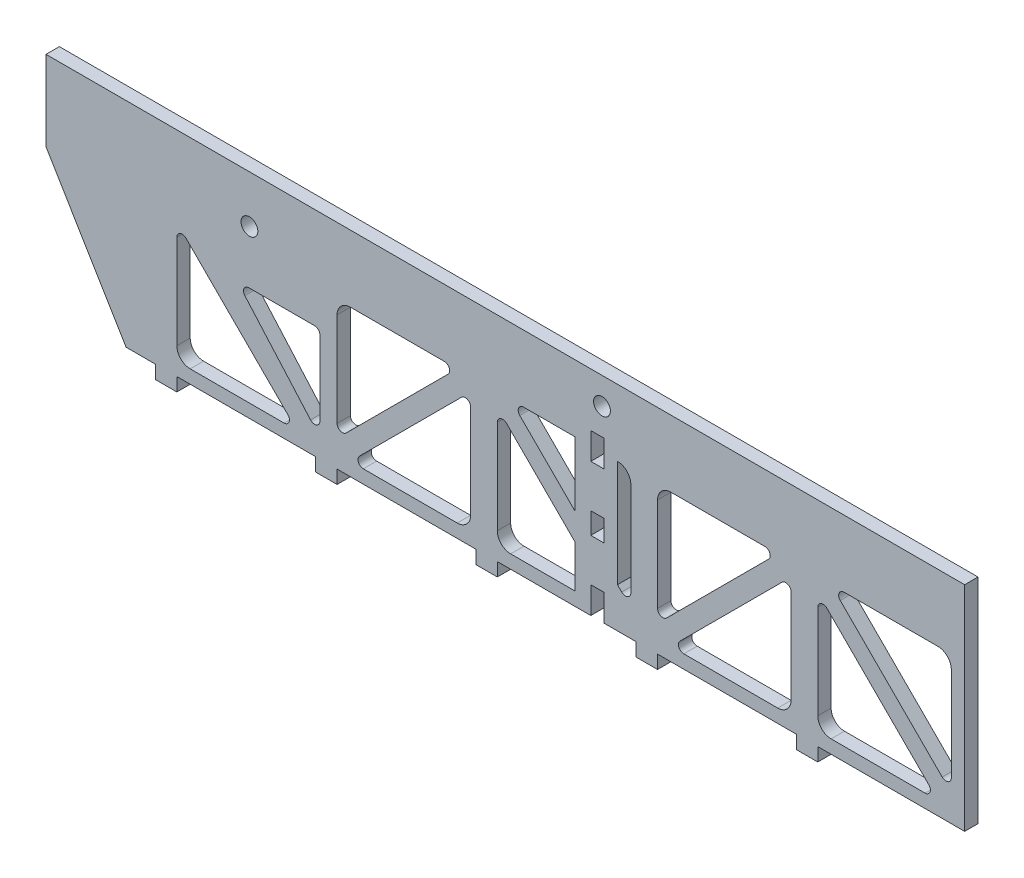
SolidWorks part; units mm, degrees
material "Pine"
ref_plane "Front Plane" through (0, 0, 0) normal (0, 0, 1) x (1, 0, 0)
ref_plane "Top Plane" through (0, 0, 0) normal (0, 1, 0) x (1, 0, 0)
ref_plane "Right Plane" through (0, 0, 0) normal (1, 0, 0) x (0, 0, -1)
sketch "Model" plane through (0, 0, 0) normal (0, 0, 1) x (1, 0, 0)
  line L0 (-306.6281, 15.625) -> (-306.6281, 51.1493)
  line L1 (-309.1681, 53.6893) -> (-340.406, 53.6893)
  line L2 (-342.3135, 49.472) -> (-311.0755, 13.9477)
  line L8 (-171.2321, 6.35) -> (-215.9, 6.35)
  line L9 (-222.25, 57.3679) -> (-222.25, 12.7)
  line L10 (-217.9139, 59.1639) -> (-169.4361, 10.6861)
  line L11 (-234.95, 57.3679) -> (-234.95, 12.7)
  line L12 (-241.3, 6.35) -> (-285.9679, 6.35)
  line L13 (-239.2861, 59.1639) -> (-287.7639, 10.6861)
  line L14 (-294.1139, 17.0361) -> (-245.6361, 65.5139)
  line L15 (-298.45, 63.5) -> (-298.45, 18.8321)
  line L16 (-247.4321, 69.85) -> (-292.1, 69.85)
  line L17 (-323.6321, 6.35) -> (-368.3, 6.35)
  line L18 (-374.65, 57.3679) -> (-374.65, 12.7)
  line L19 (-370.3139, 59.1639) -> (-321.8361, 10.6861)
  line L20 (-18.8321, 6.35) -> (-63.5, 6.35)
  line L21 (-69.85, 57.3679) -> (-69.85, 12.7)
  line L22 (-17.0361, 10.6861) -> (-65.5139, 59.1639)
  line L23 (-82.55, 57.3679) -> (-82.55, 12.7)
  line L24 (-88.9, 6.35) -> (-133.5679, 6.35)
  line L25 (-86.8861, 59.1639) -> (-135.3639, 10.6861)
  line L26 (-93.2361, 65.5139) -> (-141.7139, 17.0361)
  line L27 (-146.05, 63.5) -> (-146.05, 18.8321)
  line L28 (-95.0321, 69.85) -> (-139.7, 69.85)
  line L29 (-163.0861, 17.0361) -> (-211.5639, 65.5139)
  line L30 (-165.1, 69.85) -> (-209.7679, 69.85)
  line L31 (-158.75, 63.5) -> (-158.75, 18.8321)
  line L35 (-398.78, 0) -> (-436.88, 63.5)
  line L36 (0, 0) -> (-398.78, 0)
  line L37 (0, 0) -> (0, 95.25)
  line L38 (0, 95.25) -> (-436.88, 95.25)
  line L39 (-436.88, 63.5) -> (-436.88, 95.25)
  line L40 (-6.35, 63.5) -> (-6.35, 18.8321)
  line L41 (-59.1639, 65.5139) -> (-10.6861, 17.0361)
  line L42 (-12.7, 69.85) -> (-57.3679, 69.85)
  arc A0 (-222.25, 12.7) -> (-215.9, 6.35) centre (-215.9, 12.7) ccw
  arc A1 (-217.9139, 59.1639) -> (-222.25, 57.3679) centre (-219.71, 57.3679) ccw
  arc A2 (-171.2321, 6.35) -> (-169.4361, 10.6861) centre (-171.2321, 8.89) ccw
  arc A3 (-234.95, 57.3679) -> (-239.2861, 59.1639) centre (-237.49, 57.3679) ccw
  arc A4 (-241.3, 6.35) -> (-234.95, 12.7) centre (-241.3, 12.7) ccw
  arc A5 (-287.7639, 10.6861) -> (-285.9679, 6.35) centre (-285.9679, 8.89) ccw
  arc A6 (-245.6361, 65.5139) -> (-247.4321, 69.85) centre (-247.4321, 67.31) ccw
  arc A7 (-298.45, 18.8321) -> (-294.1139, 17.0361) centre (-295.91, 18.8321) ccw
  arc A8 (-292.1, 69.85) -> (-298.45, 63.5) centre (-292.1, 63.5) ccw
  arc A9 (-323.6321, 6.35) -> (-321.8361, 10.6861) centre (-323.6321, 8.89) ccw
  arc A10 (-374.65, 12.7) -> (-368.3, 6.35) centre (-368.3, 12.7) ccw
  arc A11 (-370.3139, 59.1639) -> (-374.65, 57.3679) centre (-372.11, 57.3679) ccw
  arc A12 (-69.85, 12.7) -> (-63.5, 6.35) centre (-63.5, 12.7) ccw
  arc A13 (-65.5139, 59.1639) -> (-69.85, 57.3679) centre (-67.31, 57.3679) ccw
  arc A14 (-18.8321, 6.35) -> (-17.0361, 10.6861) centre (-18.8321, 8.89) ccw
  arc A15 (-82.55, 57.3679) -> (-86.8861, 59.1639) centre (-85.09, 57.3679) ccw
  arc A16 (-88.9, 6.35) -> (-82.55, 12.7) centre (-88.9, 12.7) ccw
  arc A17 (-135.3639, 10.6861) -> (-133.5679, 6.35) centre (-133.5679, 8.89) ccw
  arc A18 (-93.2361, 65.5139) -> (-95.0321, 69.85) centre (-95.0321, 67.31) ccw
  arc A19 (-146.05, 18.8321) -> (-141.7139, 17.0361) centre (-143.51, 18.8321) ccw
  arc A20 (-139.7, 69.85) -> (-146.05, 63.5) centre (-139.7, 63.5) ccw
  arc A21 (-163.0861, 17.0361) -> (-158.75, 18.8321) centre (-161.29, 18.8321) ccw
  arc A22 (-209.7679, 69.85) -> (-211.5639, 65.5139) centre (-209.7679, 67.31) ccw
  arc A23 (-158.75, 63.5) -> (-165.1, 69.85) centre (-165.1, 63.5) ccw
  arc A24 (-306.6281, 15.625) -> (-311.0755, 13.9477) centre (-309.1681, 15.625) cw
  arc A25 (-340.406, 53.6893) -> (-342.3135, 49.472) centre (-340.406, 51.1493) ccw
  arc A26 (-306.6281, 51.1493) -> (-309.1681, 53.6893) centre (-309.1681, 51.1493) ccw
  arc A27 (-10.6861, 17.0361) -> (-6.35, 18.8321) centre (-8.89, 18.8321) ccw
  arc A28 (-57.3679, 69.85) -> (-59.1639, 65.5139) centre (-57.3679, 67.31) ccw
  arc A29 (-6.35, 63.5) -> (-12.7, 69.85) centre (-12.7, 63.5) ccw
  circle A30 centre (-172.466, 88.9) radius 4
  circle A31 centre (-340.148, 79.054) radius 4
  dimension "D2" = 172.466
  dimension "D4" = 8
  dimension "D5" = 167.682
  dimension "D7" = 8
  dimension "D6" = 9.846
  dimension "D8" = 2.54
  dimension "D1" = 95.25
  dimension "D3" = 6.35
extrude "Boss-Extrude1" add sketch "Model" along normal blind 6.35
sketch "Sketch1" plane through (0, 0, 6.35) normal (0, 0, 1) x (1, 0, 0)
  line L0 (-69.85, 95.25) -> (-69.85, 0) construction
  line L1 (-69.85, 57.3679) -> (-69.85, 12.7) construction
  line L2 (-398.78, 0) -> (0, 0) construction
  line L3 (-146.05, 95.25) -> (-146.05, 0) construction
  line L4 (-146.05, 63.5) -> (-146.05, 18.8321) construction
  line L5 (-222.25, 95.25) -> (-222.25, 0) construction
  line L6 (-222.25, 57.3679) -> (-222.25, 12.7) construction
  line L7 (-298.45, 95.25) -> (-298.45, 0) construction
  line L8 (-298.45, 63.5) -> (-298.45, 18.8321) construction
  line L9 (-374.65, 95.25) -> (-374.65, 0) construction
  line L10 (-374.65, 57.3679) -> (-374.65, 12.7) construction
  line L11 (0, 95.25) -> (-436.88, 95.25) construction
  line L12 (-69.85, 0) -> (-80.01, 0)
  line L13 (-69.85, 0) -> (-69.85, -6.35)
  line L14 (-69.85, -6.35) -> (-80.01, -6.35)
  line L15 (-80.01, 0) -> (-80.01, -6.35)
  line L16 (-146.05, 0) -> (-156.21, 0)
  line L17 (-146.05, 0) -> (-146.05, -6.35)
  line L18 (-146.05, -6.35) -> (-156.21, -6.35)
  line L19 (-156.21, 0) -> (-156.21, -6.35)
  line L20 (-222.25, 0) -> (-232.41, 0)
  line L21 (-222.25, 0) -> (-222.25, -6.35)
  line L22 (-222.25, -6.35) -> (-232.41, -6.35)
  line L23 (-232.41, 0) -> (-232.41, -6.35)
  line L24 (-298.45, 0) -> (-308.61, 0)
  line L25 (-298.45, 0) -> (-298.45, -6.35)
  line L26 (-298.45, -6.35) -> (-308.61, -6.35)
  line L27 (-308.61, 0) -> (-308.61, -6.35)
  line L28 (-374.65, 0) -> (-384.81, 0)
  line L29 (-374.65, 0) -> (-374.65, -6.35)
  line L30 (-374.65, -6.35) -> (-384.81, -6.35)
  line L31 (-384.81, 0) -> (-384.81, -6.35)
  line L32 (0, 0) -> (0, 95.25) construction
  line L53 (-436.88, 95.25) -> (0, 95.25)
  line L54 (-436.88, 95.25) -> (-436.88, 101.6)
  line L55 (-436.88, 101.6) -> (0, 101.6)
  line L56 (0, 95.25) -> (0, 101.6)
  dimension "D1" = 6.35
  dimension "D2" = 10.16
  dimension "D3" = 10.16
  dimension "D4" = 10.16
  dimension "D5" = 10.16
  dimension "D6" = 10.16
  dimension "D8" = 6.35
extrude "Boss-Extrude2" add sketch "Sketch1" against normal up to surface (6.35 mm away) up to face at (-168.466, 88.9, 0)
sketch "Sketch2" plane through (0, 0, 0) normal (0, 0, -1) x (-1, 0, 0)
  line L0 (158.75, 18.8321) -> (158.75, 63.5) construction
  line L1 (185.42, 69.85) -> (165.1, 69.85)
  line L2 (185.42, 69.85) -> (185.42, 0)
  line L3 (185.42, 0) -> (165.1, 0)
  line L4 (165.1, 69.85) -> (165.1, 0)
  line L6 (222.25, 0) -> (156.21, 0) construction
  line L8 (165.1, 69.85) -> (209.7679, 69.85) construction
  line L10 (156.21, -6.35) -> (146.05, -6.35) construction
  line L11 (177.8, 0) -> (171.45, 0)
  line L12 (177.8, 0) -> (177.8, 12.7)
  line L13 (177.8, 12.7) -> (171.45, 12.7)
  line L14 (171.45, 0) -> (171.45, 12.7)
  line L15 (177.8, 33.02) -> (171.45, 33.02)
  line L16 (177.8, 33.02) -> (177.8, 43.18)
  line L17 (177.8, 43.18) -> (171.45, 43.18)
  line L18 (171.45, 33.02) -> (171.45, 43.18)
  line L19 (177.8, 63.5) -> (171.45, 63.5)
  line L20 (177.8, 63.5) -> (177.8, 76.2)
  line L21 (177.8, 76.2) -> (171.45, 76.2)
  line L22 (171.45, 63.5) -> (171.45, 76.2)
  dimension "D1" = 6.35
  dimension "D2" = 20.32
  dimension "D3" = 10.16
  dimension "D4" = 12.7
  dimension "D5" = 6.35
  dimension "D6" = 20.32
  dimension "D7" = 20.32
  dimension "D8" = 12.7
  dimension "D9" = 6.35
  dimension "D10" = 6.35
extrude "Boss-Extrude3" add sketch "Sketch2" against normal up to surface (6.35 mm away) contours L4 | L19 L22 L1 L4 L3 L14 L13 L12 L2 L20 L15 L18 L17 L16 region at (-184.6925, 34.925, 0) up to face at (-319.4123, 39.5294, 6.35)
extrude "Cut-Extrude1" cut sketch "Sketch2<3>" against normal blind 6.35 contours L22 L1 L20 L21 | L14 L3 L12 L13 region at (-174.625, 73.025, 0) region at (-174.625, 6.35, 0)
sketch "Sketch2<3>" plane through (0, 0, 0) normal (0, 0, -1) x (-1, 0, 0) same geometry as "Sketch2"
equation "\"thick\"=0.25"
equation "\"D1@Boss-Extrude1\"=\"thick\""
